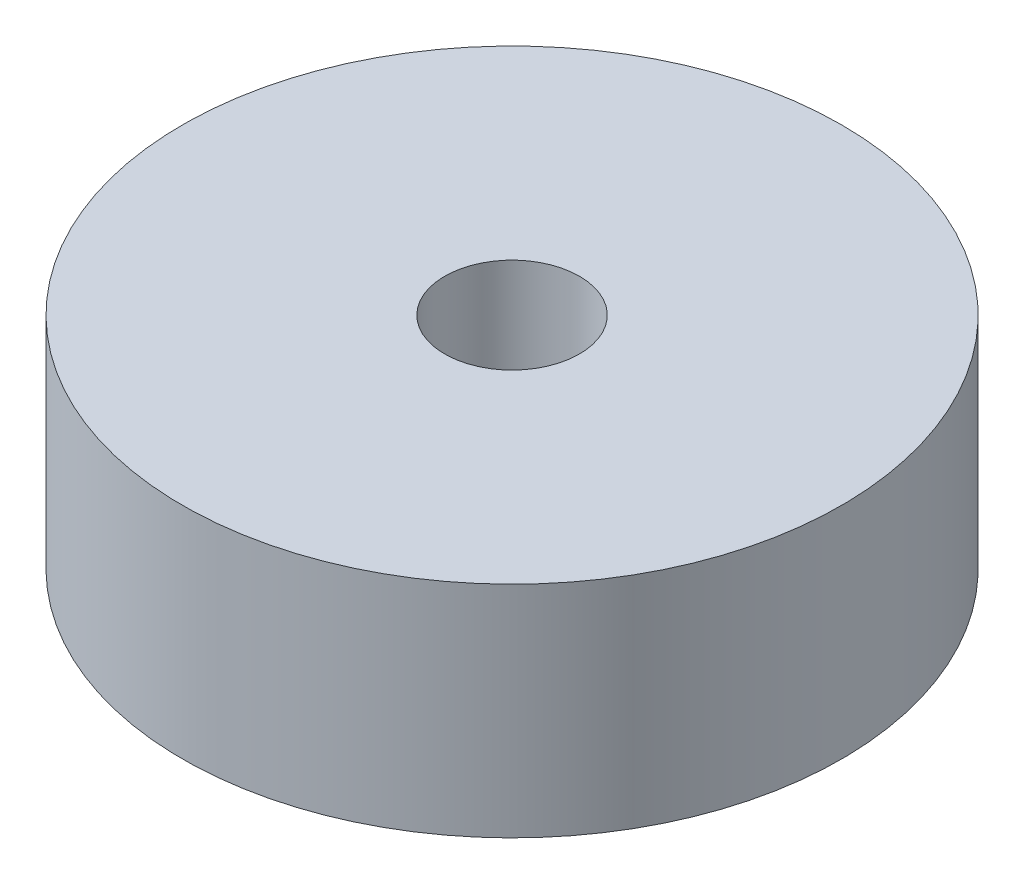
SolidWorks part; units mm, degrees
ref_plane "Front Plane" through (0, 0, 0) normal (0, 0, 1) x (1, 0, 0)
ref_plane "Top Plane" through (0, 0, 0) normal (0, 1, 0) x (1, 0, 0)
ref_plane "Right Plane" through (0, 0, 0) normal (1, 0, 0) x (0, 0, -1)
sketch "Sketch2" plane through (0, 0, 0) normal (0, 1, 0) x (1, 0, 0)
  circle A0 centre (0, 0) radius 28.575
  circle A1 centre (0, 0) radius 5.842
  dimension "D1" = 57.15
  dimension "D2" = 11.684
extrude "Boss-Extrude1" add sketch "Sketch2" along normal blind 19.05
extrude "Cut-Extrude1" cut sketch "Sketch3" against normal through all rebuild error yes
sketch "Sketch3" plane through (-18.3331, 184.6601, -46.6183) normal (-0.619, -0.0319, -0.7847) x (-0.7851, 0.0006, 0.6193)
  circle A0 centre (40.4559, -173.5345) radius 2.3495
  circle A1 centre (42.7842, 7.8054) radius 2.3495
